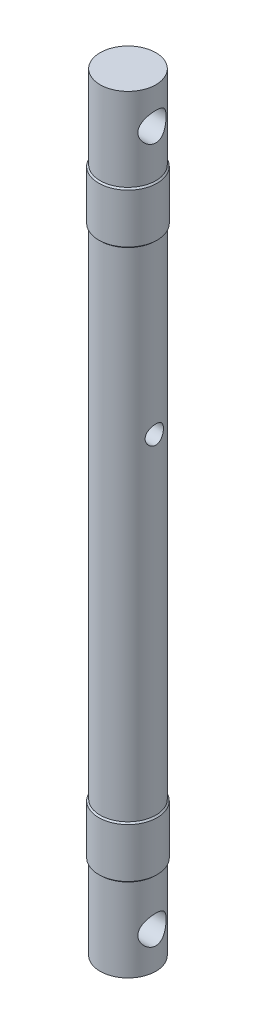
SolidWorks part; units mm, degrees
material "ABS"
ref_plane "Front Plane" through (0, 0, 0) normal (0, 0, 1) x (1, 0, 0)
ref_plane "Top Plane" through (0, 0, 0) normal (0, 1, 0) x (1, 0, 0)
ref_plane "Right Plane" through (0, 0, 0) normal (1, 0, 0) x (0, 0, -1)
sketch "Sketch1" plane through (0, 0, 0) normal (0, 1, 0) x (1, 0, 0)
  circle A0 centre (0, 0) radius 3.95
  dimension "D1" = 7.9
extrude "Boss-Extrude1" add sketch "Sketch1" along normal blind 109
hole_wizard "Ø4.0mm Dowel Hole1" positions "Sketch3" profile "Sketch4" hole size "Ø4.0" standard "ANSI Metric" end condition up to next
sketch "Sketch3" plane through (0, 0, 0) normal (1, 0, 0) x (0, 0, -1)
  line L0 (3.95, 109) -> (-3.95, 109) construction
  line L1 (-3.95, 0) -> (3.95, 0) construction
  point P0 (0, 5.15)
  point P2 (0, 103.85)
  dimension "D1" = 5.15
  dimension "D2" = 5.15
sketch "Sketch4" plane through (0, 5.15, 0) normal (0, 1, 0) x (0, 0, -1)
  line L0 (0, 0) -> (0, 3.95)
  line L1 (0, 3.95) -> (2, 3.95)
  line L2 (2, 3.95) -> (2, 0.025)
  line L3 (2, 0.025) -> (2.025, 0)
  line L5 (2.025, 0) -> (0, 0)
  line L6 (-2, 0.025) -> (-2.025, 0) construction
  line L11 (0, -6.35) -> (0, 107.95) construction
  dimension "Thru Hole Dia." = 4
  dimension "Thru Hole Depth" = 3.95
  dimension "Near C'Sink Dia." = 4.05
  dimension "Near C'Sink Angle" = 90
hole_wizard "Ø4.0mm Dowel Hole2" positions "Sketch5" profile "Sketch6" hole size "Ø4.0" standard "ANSI Metric" end condition through all
sketch "Sketch5" plane through (0, 0, 0) normal (1, 0, 0) x (0, 0, -1)
  line L0 (3.95, 109) -> (-3.95, 109) construction
  line L1 (-3.95, 0) -> (3.95, 0) construction
  point P0 (0, 103.85)
  point P2 (0, 5.15)
  dimension "D1" = 5.15
  dimension "D2" = 5.15
sketch "Sketch6" plane through (0, 103.85, 0) normal (0, 1, 0) x (0, 0, 1)
  line L0 (0, 0) -> (0, 3.95)
  line L1 (0, 3.95) -> (2, 3.95)
  line L2 (2, 3.95) -> (2, 0.025)
  line L3 (2, 0.025) -> (2.025, 0)
  line L5 (2.025, 0) -> (0, 0)
  line L6 (-2, 0.025) -> (-2.025, 0) construction
  line L11 (0, -6.35) -> (0, 107.95) construction
  dimension "Thru Hole Dia." = 4
  dimension "Thru Hole Depth" = 3.95
  dimension "Near C'Sink Dia." = 4.05
  dimension "Near C'Sink Angle" = 90
sketch "Sketch7" plane through (0, 0, 0) normal (1, 0, 0) x (0, 0, -1)
  line L0 (3.95, 0) -> (3.95, 109) construction
  line L1 (3.95, 109) -> (-3.95, 109) construction
  line L2 (3.95, 97) -> (4.15, 97)
  line L3 (3.95, 97) -> (3.95, 90)
  line L4 (3.95, 90) -> (4.15, 90)
  line L5 (4.15, 97) -> (4.15, 90)
  line L6 (0, 99.2222) -> (0, 85.4987) construction
  line L7 (-3.95, 0) -> (3.95, 0) construction
  line L8 (3.95, 19) -> (4.15, 19)
  line L9 (3.95, 19) -> (3.95, 12)
  line L10 (3.95, 12) -> (4.15, 12)
  line L11 (4.15, 19) -> (4.15, 12)
  dimension "D1" = 12
  dimension "D2" = 7
  dimension "D3" = 0.2
  dimension "D4" = 12
  dimension "D5" = 7
  dimension "D6" = 0.2
revolve "Revolve1" add sketch "Sketch7" angle 360 about L6
chamfer "Chamfer1" distance 0.2 angle 45 4 edges at (0, 90, 3.95) (0, 97, -3.95) (0, 19, -3.95) (0, 12, 3.95)
sketch "Sketch8" plane through (0, 0, 0) normal (1, 0, 0) x (0, 0, -1)
  line L1 (3.95, 109) -> (-3.95, 109) construction
  circle A0 centre (0, 66) radius 1.3
  dimension "D1" = 2.6
  dimension "D2" = 43
extrude "Cut-Extrude2" cut sketch "Sketch8" against normal through all both and the other way through all
